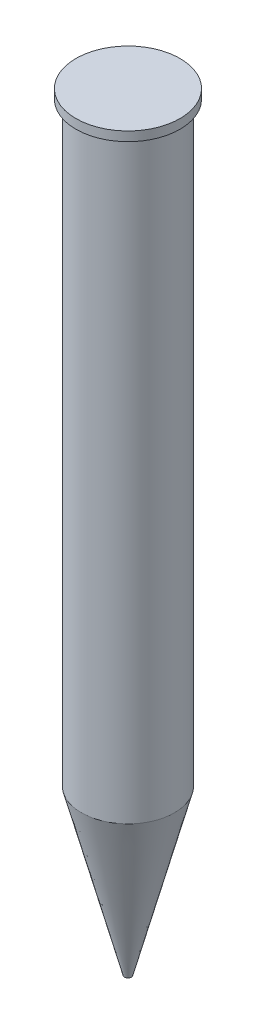
SolidWorks part; units mm, degrees
ref_plane "Front Plane" through (0, 0, 0) normal (0, 0, 1) x (1, 0, 0)
ref_plane "Top Plane" through (0, 0, 0) normal (0, 1, 0) x (1, 0, 0)
ref_plane "Right Plane" through (0, 0, 0) normal (1, 0, 0) x (0, 0, -1)
sketch "Sketch1" plane through (0, 0, 0) normal (0, 1, 0) x (1, 0, 0)
  circle A0 centre (0, 0) radius 63.5
extrude "Boss-Extrude1" add sketch "Sketch1" along normal blind 812.8
sketch "Sketch2" plane through (0, 812.8, 0) normal (0, 1, 0) x (1, 0, 0)
  circle A0 centre (0, 0) radius 71.1286
extrude "Boss-Extrude2" add sketch "Sketch2" along normal blind 12.7
sketch "Sketch5" plane through (0, 0, 0) normal (1, 0, 0) x (0, 0, -1)
  line L0 (-63.5, 0) -> (0, 0)
  line L1 (-63.5, 0) -> (63.5, 0) construction
  line L2 (0, 0) -> (0, -223.941)
  line L3 (0, -223.941) -> (-4.6894, -223.941)
  line L4 (-4.6894, -223.941) -> (-63.5, 0)
  point P6 (-26.1798, -148.61)
  point P8 (-23.0145, -165.0512)
  point P9 (-4.6894, -223.941)
revolve "Revolve2" add sketch "Sketch5" angle 360 about L2
